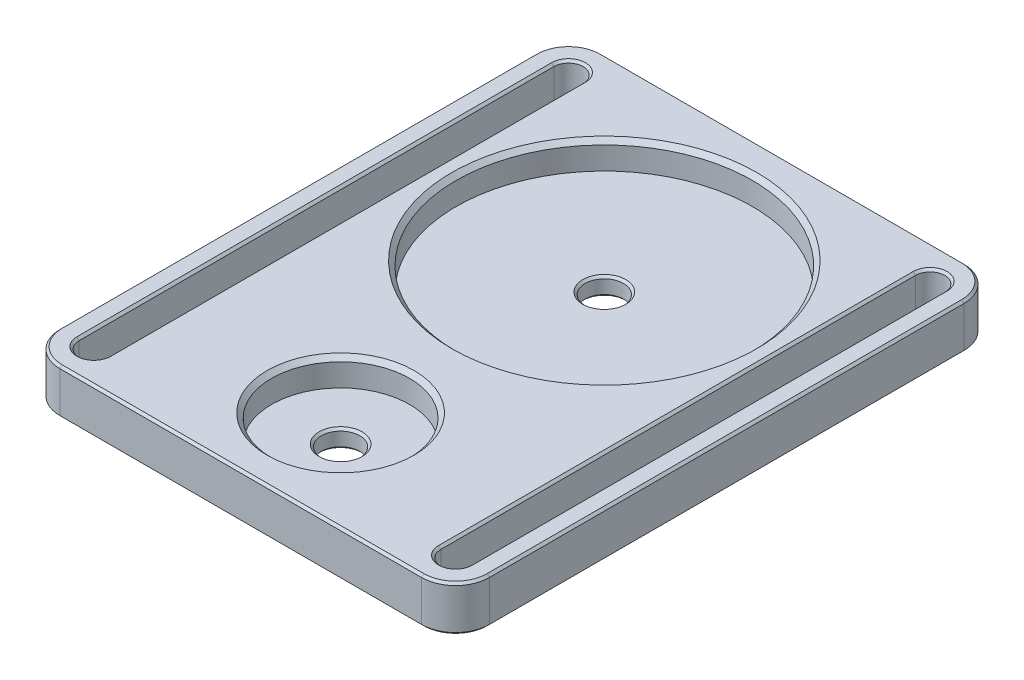
SolidWorks part; units mm, degrees
material "6061-T6 Aluminum"
ref_plane "Front Plane" through (0, 0, 0) normal (0, 0, 1) x (1, 0, 0)
ref_plane "Top Plane" through (0, 0, 0) normal (0, 1, 0) x (1, 0, 0)
ref_plane "Right Plane" through (0, 0, 0) normal (1, 0, 0) x (0, 0, -1)
sketch "Sketch1" plane through (0, 0, 0) normal (0, 1, 0) x (1, 0, 0)
  line L0 (0, 39.58) -> (0, 32.75) construction
  line L1 (-40, -80.42) -> (40, -80.42)
  line L2 (-47.5, -72.92) -> (-47.5, 32.08)
  line L3 (-40, 39.58) -> (40, 39.58)
  line L4 (47.5, -72.92) -> (47.5, 32.08)
  line L5 (0, -73.59) -> (0, -80.42) construction
  line L6 (-40, 32.08) -> (-40, -72.92) construction
  line L7 (-36.75, 32.08) -> (-36.75, -72.92)
  line L8 (-43.25, 32.08) -> (-43.25, -72.92)
  line L9 (40, 32.08) -> (40, -72.92) construction
  line L10 (43.25, 32.08) -> (43.25, -72.92)
  line L11 (36.75, 32.08) -> (36.75, -72.92)
  line L12 (-40, 0) -> (0, 0) construction
  line L13 (0, 0) -> (40, 0) construction
  line L14 (-40, -72.92) -> (-40, 32.08) construction
  line L15 (-46, -72.92) -> (-46, 32.08)
  line L16 (-34, -72.92) -> (-34, 32.08)
  line L17 (40, -72.92) -> (40, 32.08) construction
  line L18 (34, -72.92) -> (34, 32.08)
  line L19 (46, -72.92) -> (46, 32.08)
  circle A0 centre (0, 0) radius 32.75
  circle A1 centre (0, -58.34) radius 15.25
  arc A3 (-36.75, 32.08) -> (-43.25, 32.08) centre (-40, 32.08) ccw
  arc A4 (-43.25, -72.92) -> (-36.75, -72.92) centre (-40, -72.92) ccw
  arc A5 (43.25, 32.08) -> (36.75, 32.08) centre (40, 32.08) ccw
  arc A6 (36.75, -72.92) -> (43.25, -72.92) centre (40, -72.92) ccw
  circle A7 centre (0, 0) radius 4.25
  circle A8 centre (0, -58.34) radius 4.25
  arc A9 (-40, 39.58) -> (-47.5, 32.08) centre (-40, 32.08) ccw
  arc A11 (47.5, 32.08) -> (40, 39.58) centre (40, 32.08) ccw
  arc A12 (-47.5, -72.92) -> (-40, -80.42) centre (-40, -72.92) ccw
  arc A13 (40, -80.42) -> (47.5, -72.92) centre (40, -72.92) ccw
  arc A14 (-46, -72.92) -> (-34, -72.92) centre (-40, -72.92) ccw
  arc A15 (-34, 32.08) -> (-46, 32.08) centre (-40, 32.08) ccw
  arc A16 (34, -72.92) -> (46, -72.92) centre (40, -72.92) ccw
  arc A17 (46, 32.08) -> (34, 32.08) centre (40, 32.08) ccw
  point P0 (0, 0)
  point P2 (-40, -20.42)
  point P17 (-40, -20.42)
  point P22 (40, -20.42)
  point P46 (40, -20.42)
  dimension "D1" = 30.5
  dimension "D2" = 65.5
  dimension "D5" = 8.5
  dimension "D3" = 58.34
  dimension "D4" = 6.5
  dimension "D6" = 80
  dimension "D7" = 12
  dimension "D8" = 95
  dimension "D9" = 120
extrude "Boss-Extrude1" add sketch "Sketch1" along normal blind 10 contours L1 A13 L4 A11 L3 A9 L2 A12 A17 L19 A16 L18 A15 L16 A14 L15 A0 A1 | A0 A7 | A1 A8 | L11 A6 L10 A5 | L16 A15 L15 A14 A4 L8 A3 L7 | L19 A17 L18 A16 A6 L11 A5 L10 | L8 A4 L7 A3 | A7 | A8 region at (-45.1951, 0, 78.1151) region at (-40, 0, 20.42) region at (40, 0, 20.42) region at (-44.8239, 0, 20.42) region at (35.1761, 0, 20.42) region at (-31.8237, 0, 0) region at (-14.8187, 0, 58.34) region at (0, 0, 0) region at (0, 0, 58.34)
extrude "Cut-Extrude2" cut sketch "Sketch1<4>" along normal through all contours L11 A6 L10 A5 | A7 | A8 | L8 A4 L7 A3 region at (-40, 0, 20.42) region at (40, 0, 20.42) region at (0, 0, 0) region at (0, 0, 58.34)
sketch "Sketch1<4>" plane through (0, 0, 0) normal (0, 1, 0) x (1, 0, 0) same geometry as "Sketch1"
extrude "Cut-Extrude3" cut sketch "Sketch1<6>" along normal through all from offset 4 contours A0 A7 | A1 A8 region at (-31.8237, 0, 0) region at (-14.8187, 0, 58.34)
sketch "Sketch1<6>" plane through (0, 0, 0) normal (0, 1, 0) x (1, 0, 0) same geometry as "Sketch1"
chamfer "Chamfer1" distance 1 angle 45 2 edges at (0, 10, 73.59) (0, 10, 32.75)
chamfer "Chamfer2" distance 0.5 angle 45 36 edges at (0, 4, 62.59) (0, 0, 62.59) (0, 4, 4.25) (0, 0, 4.25) (43.25, 10, 20.42) (40, 10, -35.33) (40, 10, 76.17) (36.75, 10, 20.42) (43.25, 0, 20.42) (40, 0, -35.33) (40, 0, 76.17) (36.75, 0, 20.42) (-36.75, 10, 20.42) (-40, 10, -35.33) (-40, 10, 76.17) (-43.25, 10, 20.42) (-36.75, 0, 20.42) (-40, 0, -35.33) (-40, 0, 76.17) (-43.25, 0, 20.42) (0, 10, -39.58) (-45.3033, 10, -37.3833) (45.3033, 10, -37.3833) (-47.5, 10, 20.42) (47.5, 10, 20.42) (-45.3033, 10, 78.2233) (45.3033, 10, 78.2233) (0, 10, 80.42) (0, 0, -39.58) (-45.3033, 0, -37.3833) (45.3033, 0, -37.3833) (-47.5, 0, 20.42) (47.5, 0, 20.42) (-45.3033, 0, 78.2233) (45.3033, 0, 78.2233) (0, 0, 80.42)
